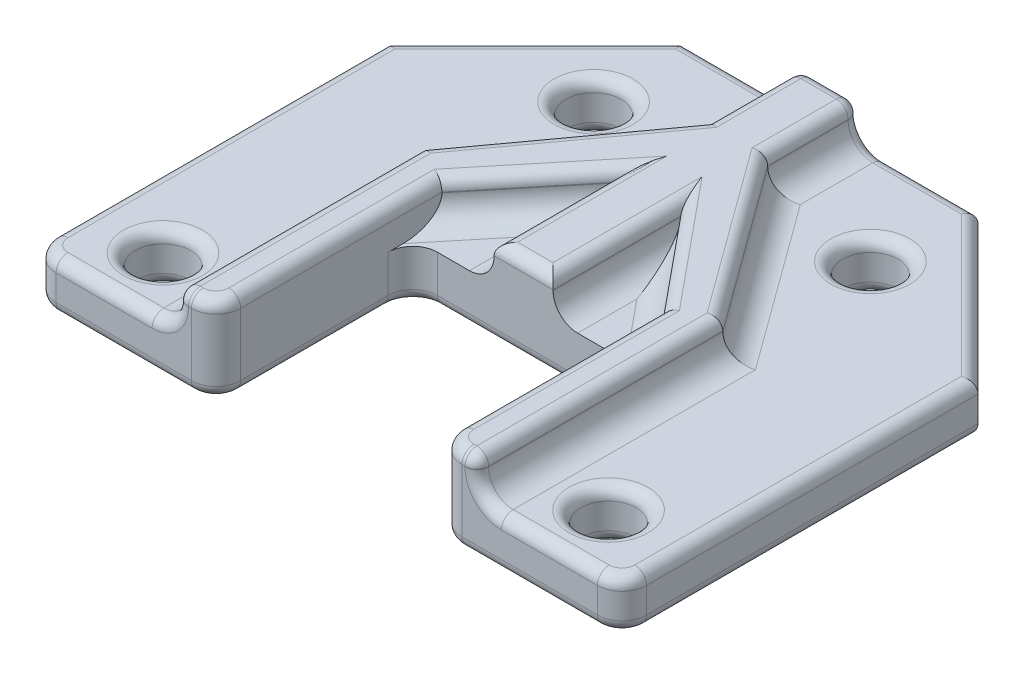
SolidWorks part; units mm, degrees
material "ABS"
ref_plane "Front" through (0, 0, 0) normal (0, 0, 1) x (1, 0, 0)
ref_plane "Top" through (0, 0, 0) normal (0, 1, 0) x (1, 0, 0)
ref_plane "Right" through (0, 0, 0) normal (1, 0, 0) x (0, 0, -1)
ref_axis "Axis1" through (0, 0, 55) along (0, 0, -1)
sketch "Sketch1" plane through (0, 0, 0) normal (0, 1, 0) x (1, 0, 0)
  line L0 (-38.1, 0) -> (-14.2875, 0)
  line L1 (-38.1, 0) -> (-38.1, 65)
  line L2 (-38.1, 65) -> (38.1, 65)
  line L3 (38.1, 65) -> (38.1, 0)
  line L4 (14.2875, 0) -> (38.1, 0)
  line L5 (0, 0) -> (0, 65) construction
  line L6 (-14.2875, 0) -> (-14.2875, 25.4)
  line L7 (-14.2875, 25.4) -> (14.2875, 25.4)
  line L8 (14.2875, 25.4) -> (14.2875, 0)
  arc A0 (14.2875, 0) -> (-14.2875, 0) centre (0, 0) ccw construction
  point P9 (0, 65)
  dimension "D1" = 28.575
  dimension "D2" = 65
  dimension "D3" = 76.2
  dimension "D4" = 25.4
extrude "Boss-Extrude1" add sketch "Sketch1" along normal blind 6.35
hole_wizard "1/4 Clearance Hole1" positions "Sketch2" profile "Sketch3" hole size "1/4" standard "ANSI Inch" end condition through all
sketch "Sketch2" plane through (0, 6.35, 0) normal (0, 1, 0) x (1, 0, 0)
  line L0 (-17.8625, 52.3) -> (17.8625, 52.3) construction
  line L2 (38.1, 65) -> (-38.1, 65) construction
  line L3 (0, 65) -> (0, 0) construction
  line L6 (-28.75, 7.62) -> (28.75, 7.62) construction
  line L8 (-38.1, 0) -> (-14.2875, 0) construction
  point P0 (-28.75, 7.62)
  point P2 (28.75, 7.62)
  point P4 (17.8625, 52.3)
  point P6 (-17.8625, 52.3)
  point P20 (0, 52.3)
  point P28 (0, 7.62)
  dimension "D1" = 12.7
  dimension "D2" = 57.5
  dimension "D3" = 7.62
  dimension "D4" = 35.725
sketch "Sketch3" plane through (-28.75, 6.35, -7.62) normal (1, 0, 0) x (0, 0, 1)
  line L0 (0, 0) -> (0, 6.35)
  line L1 (0, 6.35) -> (3.5712, 6.35)
  line L2 (3.5712, 6.35) -> (3.5712, 0)
  line L5 (3.5712, 0) -> (0, 0)
  line L11 (0, -6.35) -> (0, 107.95) construction
  dimension "Thru Hole Dia." = 7.1425
  dimension "Thru Hole Depth" = 6.35
fillet "Fillet1" radius 3.175 2 edges at (14.2875, 3.175, -25.4) (-14.2875, 3.175, -25.4)
sketch "Sketch4" plane through (0, 6.35, 0) normal (0, 1, 0) x (1, 0, 0)
  line L0 (0, 65) -> (0, 25.4) construction
  line L1 (38.1, 65) -> (-38.1, 65) construction
  line L2 (-11.1125, 25.4) -> (11.1125, 25.4) construction
  line L3 (-14.2875, 29.1506) -> (-3.81, 41.91)
  line L4 (-14.2875, 0) -> (-19.3675, 0)
  line L5 (-14.2875, 0) -> (-14.2875, 29.1506)
  line L7 (-19.3675, 0) -> (-19.3675, 31.75)
  line L8 (14.2875, 0) -> (19.3675, 0)
  line L9 (14.2875, 0) -> (14.2875, 29.1506)
  line L11 (19.3675, 0) -> (19.3675, 31.75)
  line L12 (-3.81, 65) -> (3.81, 65)
  line L13 (-3.81, 65) -> (-3.81, 53.0988)
  line L14 (-3.81, 25.4) -> (3.81, 25.4)
  line L15 (3.81, 65) -> (3.81, 53.0988)
  line L16 (-19.3675, 31.75) -> (-3.81, 53.0988)
  line L17 (14.2875, 29.1506) -> (3.81, 41.91)
  line L18 (19.3675, 31.75) -> (3.81, 53.0988)
  line L19 (-3.81, 41.91) -> (-3.81, 25.4)
  line L20 (3.81, 41.91) -> (3.81, 25.4)
  point P20 (0, 65)
  dimension "D1" = 7.62
  dimension "D2" = 31.75
  dimension "D3" = 5.08
  dimension "D4" = 26.416
  dimension "D5" = 16.51
  dimension "D6" = 16.51
extrude "Boss-Extrude2" add sketch "Sketch4" along normal blind 4.7752
chamfer "Chamfer1" distance 19.05 angle 45 2 edges at (-38.1, 3.175, -65) (38.1, 3.175, -65)
fillet "Fillet2" radius 3.175 14 edges at (14.2875, 5.5626, 0) (-14.2875, 5.5626, 0) (38.1, 3.175, 0) (-38.1, 3.175, 0) (-9.0488, 6.35, -35.5303) (-3.81, 6.35, -33.655) (3.81, 6.35, -33.655) (9.0488, 6.35, -35.5303) (19.3675, 6.35, -15.875) (11.5888, 6.35, -42.4244) (3.81, 6.35, -59.0494) (-3.81, 6.35, -59.0494) (-11.5888, 6.35, -42.4244) (-19.3675, 6.35, -15.875)
fillet "Fillet3" radius 1.524 18 edges at (-18.415, 11.1252, 0) (-14.2875, 11.1252, -16.1628) (18.415, 11.1252, 0) (15.2174, 11.1252, -0.9299) (0, 11.1252, -65) (9.0488, 11.1252, -35.5303) (3.81, 11.1252, -33.655) (-3.81, 11.1252, -33.655) (-9.0488, 11.1252, -35.5303) (-15.2174, 11.1252, -0.9299) (14.2875, 11.1252, -16.1628) (19.3675, 11.1252, -15.875) (11.5888, 11.1252, -42.4244) (3.81, 11.1252, -59.0494) (-3.81, 11.1252, -59.0494) (-11.5888, 11.1252, -42.4244) (-19.3675, 11.1252, -15.875) (0, 11.1252, -25.4)
fillet "Fillet4" radius 1.524 46 edges at (3.3636, 10.6788, -64.5536) (3.81, 9.5631, -65) (4.7399, 7.2799, -65) (18.9211, 10.6788, -0.4464) (19.3675, 9.5631, 0) (20.2974, 7.2799, 0) (-3.3636, 10.6788, -64.5536) (-3.81, 9.5631, -65) (-4.7399, 7.2799, -65) (-18.9211, 10.6788, -0.4464) (-19.3675, 9.5631, 0) (-20.2974, 7.2799, 0) (37.1701, 0, -0.9299) (38.1, 0, -24.5625) (28.575, 0, -55.475) (0, 0, -65) (-28.575, 0, -55.475) (-38.1, 0, -24.5625) (-37.1701, 0, -0.9299) (-26.1938, 0, 0) (-15.2174, 0, -0.9299) (-14.2875, 0, -12.7) (-13.3576, 0, -24.4701) (0, 0, -25.4) (13.3576, 0, -24.4701) (14.2875, 0, -12.7) (15.2174, 0, -0.9299) (26.1938, 0, 0) (-17.8625, 0, -48.7288) (17.8625, 0, -48.7288) (28.75, 0, -4.0488) (-28.75, 0, -4.0488) (13.0175, 6.35, -65) (28.575, 6.35, -55.475) (38.1, 6.35, -24.5625) (37.1701, 6.35, -0.9299) (28.7338, 6.35, 0) (28.75, 6.35, -4.0488) (17.8625, 6.35, -48.7288) (-28.575, 6.35, -55.475) (-13.0175, 6.35, -65) (-28.7338, 6.35, 0) (-37.1701, 6.35, -0.9299) (-38.1, 6.35, -24.5625) (-28.75, 6.35, -4.0488) (-17.8625, 6.35, -48.7288)
